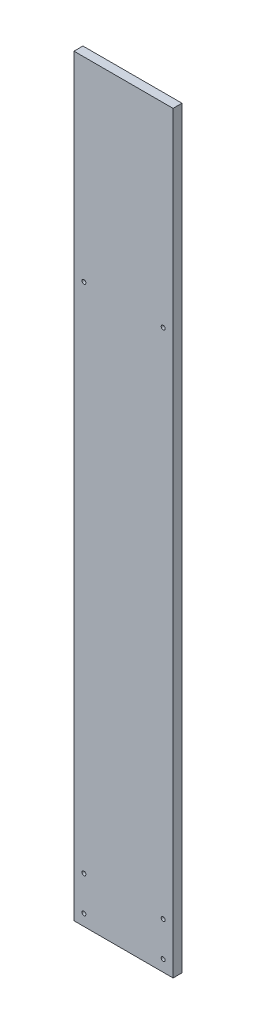
SolidWorks part; units mm, degrees
ref_plane "Front Plane" through (0, 0, 0) normal (0, 0, 1) x (1, 0, 0)
ref_plane "Top Plane" through (0, 0, 0) normal (0, 1, 0) x (1, 0, 0)
ref_plane "Right Plane" through (0, 0, 0) normal (1, 0, 0) x (0, 0, -1)
sketch "Sketch1" plane through (0, 0, 0) normal (0, 0, 1) x (1, 0, 0)
  line L0 (-330.3006, 181.5669) -> (-30.3006, 181.5669) construction
  line L1 (-230.3006, 181.5669) -> (-130.3006, 181.5669)
  line L2 (-230.3006, 181.5669) -> (-230.3006, -578.4331)
  line L3 (-230.3006, -578.4331) -> (-130.3006, -578.4331)
  line L4 (-130.3006, 181.5669) -> (-130.3006, -578.4331)
  line L5 (-33.3006, -578.4331) -> (-70.3006, -578.4331) construction
  line L6 (-180.3006, 181.5669) -> (-180.3006, -578.4331) construction
  line L7 (-230.3006, -198.4331) -> (-180.3006, -198.4331) construction
  line L8 (-180.3006, -198.4331) -> (-130.3006, -198.4331) construction
  dimension "D1" = 100
extrude "Boss-Extrude1" add sketch "Sketch1" along normal blind 9
hole_wizard "Ø4.0 (4) Diameter Hole1" positions "Sketch2" profile "Sketch3" hole size "Ø4.0" standard "ISO" end condition through all
sketch "Sketch2" plane through (-171.5962, -73.097, 9) normal (0, 0, 1) x (1, 0, 0)
  point P0 (-48.7044, -458.8361)
  point P3 (-48.7044, -493.8361)
  point P6 (31.2956, -493.8361)
  point P9 (31.2956, -458.8361)
  point P12 (31.2956, 58.0784)
  point P15 (-48.7044, 58.0784)
sketch "Sketch3" plane through (-220.3006, -531.9331, 9) normal (1, 0, 0) x (0, -1, 0)
  line L0 (0, 0) -> (0, 9)
  line L1 (0, 9) -> (2, 9)
  line L2 (2, 9) -> (2, 0)
  line L3 (2, 0) -> (0, 0)
  line L4 (0, -6.35) -> (0, 107.95) construction
  dimension "Thru Hole Dia." = 4
  dimension "Thru Hole Depth" = 9
